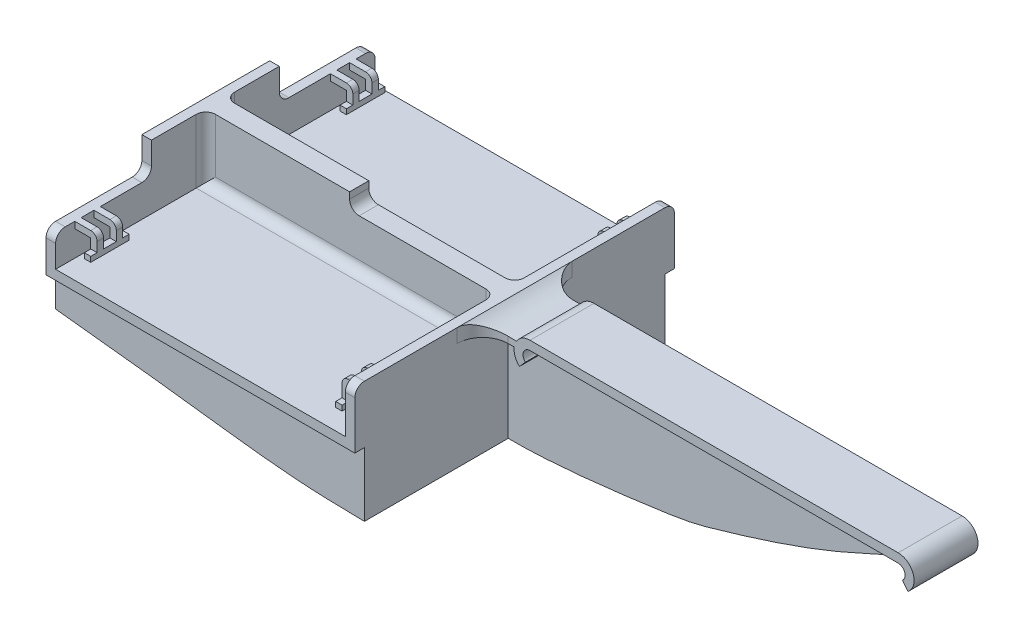
SolidWorks part; units mm, degrees
ref_plane "Piano frontale" through (0, 0, 0) normal (0, 0, 1) x (1, 0, 0)
ref_plane "Piano superiore" through (0, 0, 0) normal (0, 1, 0) x (1, 0, 0)
ref_plane "Piano destro" through (0, 0, 0) normal (1, 0, 0) x (0, 0, -1)
sketch "Schizzo1" plane through (0, 0, 0) normal (0, 0, 1) x (1, 0, 0)
  line L0 (11.7177, -12.3971) -> (506.3844, -12.3971) construction
  line L3 (25.2883, 10.9435) -> (25.2883, 30.9435)
  line L4 (118.9283, 25.9435) -> (118.9283, 7.9435)
  line L5 (118.9283, 7.9435) -> (22.2883, 7.9435)
  line L6 (115.9283, 25.9435) -> (115.9283, 10.9435)
  line L7 (115.9283, 10.9435) -> (25.2883, 10.9435)
  line L8 (22.2883, 7.9435) -> (22.2883, 30.9435)
  line L9 (22.2883, 30.9435) -> (25.2883, 30.9435)
  line L10 (115.9283, 25.9435) -> (118.9283, 25.9435)
  dimension "D1" = 90.64
  dimension "D2" = 20
  dimension "D3" = 15
  dimension "D4" = 3
extrude "Estrusione-Estrusione1" add sketch "Schizzo1" along normal blind 50
sketch "Schizzo2" plane through (25.2883, 0, 0) normal (1, 0, 0) x (0, 0, -1)
  line L0 (-50, 20.9435) -> (-20, 20.9435)
  line L1 (-50, 10.9435) -> (-50, 30.9435) construction
  line L2 (-20, 20.9435) -> (-20, 30.9435)
  line L3 (-50, 30.9435) -> (0, 30.9435) construction
  line L4 (-20, 30.9435) -> (-50, 30.9435)
  line L5 (-50, 30.9435) -> (-50, 20.9435)
  dimension "D1" = 30
  dimension "D2" = 10
extrude "Taglio-Estrusione2" cut sketch "Schizzo2" against normal blind 3
fillet "Raccordo1" radius 3 1 edges at (23.7883, 20.9435, 20)
sketch "Schizzo3" plane through (0, 0, 0) normal (0, 0, -1) x (-1, 0, 0)
  line L0 (-25.2883, 30.9435) -> (-70.2883, 30.9435)
  line L1 (-70.2883, 30.9435) -> (-70.2883, 25.9435)
  line L2 (-70.2883, 25.9435) -> (-115.9283, 25.9435)
  line L3 (-115.9283, 25.9435) -> (-115.9283, 10.9435)
  line L4 (-115.9283, 25.9435) -> (-115.9283, 10.9435) construction
  line L5 (-115.9283, 10.9435) -> (-25.2883, 10.9435) construction
  line L6 (-115.9283, 10.9435) -> (-25.2883, 10.9435)
  line L7 (-25.2883, 10.9435) -> (-25.2883, 30.9435)
  dimension "D1" = 45
  dimension "D2" = 5
extrude "Estrusione-Estrusione2" add sketch "Schizzo3" against normal blind 3
mirror "Specchia1" about plane through (0, 0, 0) normal (0, 0, 1) of "Estrusione-Estrusione2", "Raccordo1", "Taglio-Estrusione2", "Estrusione-Estrusione1"
fillet "Raccordo2" radius 3 7 edges at (70.6083, 10.9435, 3) (70.6083, 10.9435, -3) (115.9283, 18.4435, -3) (115.9283, 18.4435, 3) (70.2883, 25.9435, 0) (25.2883, 20.9435, -3) (25.2883, 20.9435, 3)
sketch "Schizzo4" plane through (25.2883, 0, 0) normal (1, 0, 0) x (0, 0, -1)
  line L0 (-44, 20.9435) -> (-44, 18.9435)
  line L1 (-50, 20.9435) -> (-23, 20.9435) construction
  line L2 (-44, 18.9435) -> (-42, 18.9435)
  line L3 (-42, 18.9435) -> (-42, 20.9435)
  line L4 (-42, 20.9435) -> (-44, 20.9435)
  line L5 (-38, 20.9435) -> (-38, 18.9435)
  line L6 (-38, 18.9435) -> (-36, 18.9435)
  line L7 (-36, 18.9435) -> (-36, 20.9435)
  line L8 (-36, 20.9435) -> (-38, 20.9435)
  dimension "D1" = 2
  dimension "D2" = 2
  dimension "D3" = 2
  dimension "D4" = 2
  dimension "D5" = 6
  dimension "D6" = 4
extrude "Estrusione-Estrusione3" add sketch "Schizzo4" along normal blind 7
sketch "Schizzo6" plane through (0, 18.9435, 0) normal (0, -1, 0) x (1, 0, 0)
  line L0 (32.2883, 44) -> (25.2883, 44) construction
  line L1 (30.2883, 44) -> (32.2883, 44)
  line L2 (30.2883, 44) -> (30.2883, 42)
  line L3 (30.2883, 42) -> (32.2883, 42)
  line L4 (32.2883, 44) -> (32.2883, 42)
  line L5 (32.2883, 38) -> (25.2883, 38) construction
  line L6 (30.2883, 38) -> (32.2883, 38)
  line L7 (30.2883, 38) -> (30.2883, 36)
  line L8 (30.2883, 36) -> (32.2883, 36)
  line L9 (32.2883, 38) -> (32.2883, 36)
  dimension "D1" = 2
  dimension "D2" = 2
extrude "Estrusione-Estrusione5" add sketch "Schizzo6" along normal blind 3
sketch "Schizzo7" plane through (0, 15.9435, 0) normal (0, -1, 0) x (1, 0, 0)
  line L0 (32.2883, 34) -> (32.2883, 46)
  line L1 (32.2883, 46) -> (30.2883, 46)
  line L2 (30.2883, 46) -> (30.2883, 34)
  line L3 (30.2883, 34) -> (32.2883, 34)
  line L4 (32.2883, 36) -> (32.2883, 38) construction
  line L6 (30.2883, 38) -> (30.2883, 36) construction
  dimension "D1" = 2
  dimension "D2" = 2
extrude "Estrusione-Estrusione6" add sketch "Schizzo7" along normal blind 1.62
sketch "Schizzo8" plane through (115.9283, 0, 0) normal (-1, 0, 0) x (0, 0, 1)
  line L0 (50, 10.9435) -> (6, 10.9435) construction
  line L1 (42, 18.9435) -> (44, 18.9435)
  line L2 (42, 18.9435) -> (42, 20.9435)
  line L3 (42, 20.9435) -> (44, 20.9435)
  line L4 (44, 18.9435) -> (44, 20.9435)
  line L5 (36, 20.9435) -> (38, 20.9435)
  line L6 (36, 20.9435) -> (36, 18.9435)
  line L7 (36, 18.9435) -> (38, 18.9435)
  line L8 (38, 20.9435) -> (38, 18.9435)
  line L9 (50, 25.9435) -> (50, 10.9435) construction
  dimension "D1" = 8
  dimension "D2" = 8
  dimension "D3" = 6
  dimension "D4" = 2
  dimension "D5" = 4
  dimension "D6" = 2
  dimension "D7" = 2
  dimension "D8" = 2
extrude "Estrusione-Estrusione7" add sketch "Schizzo8" along normal blind 7
sketch "Schizzo9" plane through (0, 18.9435, 0) normal (0, -1, 0) x (1, 0, 0)
  line L0 (108.9283, 42) -> (115.9283, 42) construction
  line L1 (108.9283, 44) -> (110.9283, 44)
  line L2 (108.9283, 44) -> (108.9283, 42)
  line L3 (108.9283, 42) -> (110.9283, 42)
  line L4 (110.9283, 44) -> (110.9283, 42)
  line L5 (108.9283, 36) -> (115.9283, 36) construction
  line L6 (108.9283, 38) -> (110.9283, 38)
  line L7 (108.9283, 38) -> (108.9283, 36)
  line L8 (108.9283, 36) -> (110.9283, 36)
  line L9 (110.9283, 38) -> (110.9283, 36)
  dimension "D1" = 2
  dimension "D2" = 2
extrude "Estrusione-Estrusione8" add sketch "Schizzo9" along normal blind 4
sketch "Schizzo10" plane through (0, 14.9435, 0) normal (0, -1, 0) x (1, 0, 0)
  line L0 (108.9283, 46) -> (108.9283, 34)
  line L1 (108.9283, 34) -> (110.9283, 34)
  line L2 (110.9283, 34) -> (110.9283, 46)
  line L3 (110.9283, 46) -> (108.9283, 46)
  line L4 (110.9283, 42) -> (110.9283, 44) construction
  dimension "D1" = 2
  dimension "D2" = 2
extrude "Estrusione-Estrusione9" add sketch "Schizzo10" along normal blind 1.62
mirror "Specchia2" about plane through (0, 0, 0) normal (0, 0, 1) of "Estrusione-Estrusione3", "Estrusione-Estrusione5", "Estrusione-Estrusione6", "Estrusione-Estrusione7", "Estrusione-Estrusione8", "Estrusione-Estrusione9"
sketch "Schizzo11" plane through (0, 7.9435, 0) normal (0, -1, 0) x (1, 0, 0)
  line L0 (22.2883, 47) -> (118.9283, 47)
  line L1 (22.2883, 50) -> (22.2883, -50) construction
  line L2 (118.9283, 50) -> (118.9283, -50) construction
  line L4 (118.9283, -47) -> (22.2883, -47)
  line L6 (22.2883, 50) -> (118.9283, 50) construction
  line L7 (22.2883, -50) -> (118.9283, -50) construction
  line L8 (22.2883, 47) -> (22.2883, -47)
  line L9 (118.9283, 47) -> (118.9283, -47)
  dimension "D1" = 3
  dimension "D2" = 3
extrude "Estrusione-Estrusione10" add sketch "Schizzo11" along normal blind 20
sketch "Schizzo12" plane through (0, 0, 47) normal (0, 0, 1) x (1, 0, 0)
  line L0 (13.3941, 1.1199) -> (178.0607, 1.1199) construction
  line L1 (41.1667, 66) -> (205.8333, 66) construction
sketch "Schizzo13" plane through (0, 0, -47) normal (0, 0, -1) x (-1, 0, 0)
  line L0 (25.0297, 53.209) -> (189.6964, 53.209) construction
  line L1 (-22.2883, -12.0565) -> (-22.2883, 7.9435) construction
  line L2 (-118.9283, -12.0565) -> (-22.2883, -12.0565)
  line L3 (-22.2883, -12.0565) -> (-22.2883, -2.8385)
  spline S0 degree 3 poles (-118.9283, -12.0565) (-113.3221, -11.9609) (-97.1539, -11.7038) (-74.9047, -8.9689) (-56.9861, -6.6502) (-40.6543, -4.941) (-29.9124, -3.6877) (-22.2883, -2.8385) knots 0 0 0 0 0.167378 0.482025 0.664557 0.712915 0.965609 0.965609 0.965609 0.965609
extrude "Taglio-Estrusione3" cut sketch "Schizzo13" against normal through all
fillet "Raccordo3" radius 2 8 edges at (32.2883, 20.9435, -37) (32.2883, 20.9435, -43) (108.9283, 20.9435, -37) (108.9283, 20.9435, -43) (108.9283, 20.9435, 37) (108.9283, 20.9435, 43) (32.2883, 20.9435, 43) (32.2883, 20.9435, 37)
sketch "Schizzo15" plane through (118.9283, 0, 0) normal (1, 0, 0) x (0, 0, -1)
  line L0 (0, 25.9435) -> (0, -12.0565) construction
  line L1 (-50, 25.9435) -> (50, 25.9435) construction
  line L2 (47, -12.0565) -> (-47, -12.0565) construction
  line L3 (-2, 25.9435) -> (-2, -13.0023)
  line L5 (2, -13.0023) -> (2, 25.9435)
  line L6 (2, 25.9435) -> (-2, 25.9435)
  line L7 (-2, -13.0023) -> (2, -13.0023)
  dimension "D1" = 2
  dimension "D2" = 2
extrude "Estrusione-Estrusione11" add sketch "Schizzo15" along normal blind 130
sketch "Schizzo16" plane through (0, 0, 2) normal (0, 0, 1) x (1, 0, 0)
  line L0 (248.9283, 25.9435) -> (248.9283, -13.0023) construction
  line L1 (118.9283, -12.0565) -> (118.9283, -13.0023)
  line L2 (118.9283, -13.0023) -> (248.9283, -13.0023)
  line L4 (248.9283, 20.2619) -> (252.8557, 20.2619)
  line L5 (252.8557, 20.2619) -> (252.8557, -13.0023)
  line L6 (252.8557, -13.0023) -> (248.9283, -13.0023)
  spline S0 degree 3 poles (118.9283, -12.0565) (129.6329, -12.2391) (148.9463, -10.2664) (174.9517, -6.6591) (178.1917, -5.9645) (202.7333, 1.4455) (223.4437, 8.7439) (238.8353, 16.6288) (248.9283, 20.2619) knots 0 0 0 0 0.253782 0.311898 0.551242 0.605271 0.822265 1 1 1 1
  spline S1 degree 3 poles (22.2883, -2.8385) (29.9124, -3.6877) (40.6543, -4.941) (56.9861, -6.6502) (74.9047, -8.9689) (97.1539, -11.7038) (113.3221, -11.9609) (118.9283, -12.0565) knots 0 0 0 0 0.252694 0.301053 0.483585 0.798232 0.965609 0.965609 0.965609 0.965609 construction
extrude "Taglio-Estrusione4" cut sketch "Schizzo16" against normal through all
sketch "Schizzo18" plane through (0, 0, 2) normal (0, 0, 1) x (1, 0, 0)
  line L1 (133.7863, 25.9435) -> (118.9283, 25.9435)
  line L2 (248.9283, 25.9435) -> (118.9283, 25.9435) construction
  line L3 (133.7863, 25.9435) -> (133.7863, 23.5598)
  line L4 (133.7863, 23.5598) -> (118.9283, 23.5598)
  line L5 (118.9283, 7.9435) -> (118.9283, 25.9435) construction
  line L6 (118.9283, 23.5598) -> (118.9283, 25.9435)
extrude "Taglio-Estrusione5" cut sketch "Schizzo18" against normal through all
sketch "Schizzo19" plane through (0, 0, 2) normal (0, 0, 1) x (1, 0, 0)
  line L0 (133.7512, 20.9435) -> (248.9283, 20.9435) construction
  line L1 (130.4495, 17.1887) -> (133.7512, 20.9435) construction
  line L2 (133.7512, 25.9435) -> (248.9283, 25.9435)
  line L4 (248.9283, 25.9435) -> (133.7863, 25.9435) construction
  line L7 (248.9283, 25.9435) -> (248.9283, 20.2619) construction
  line L8 (248.9283, 20.9435) -> (252.0069, 17.0036) construction
  arc A0 (133.7512, 25.9435) -> (130.4495, 17.1887) centre (133.7512, 20.9435) ccw
  arc A1 (252.0069, 17.0036) -> (248.9283, 25.9435) centre (248.9283, 20.9435) ccw
  point P4 (191.3398, 20.9435)
extrude "Estrusione-Sottile1" add sketch "Schizzo19" along normal blind 8 and the other way blind 12 thin thin type one direction reverse wall 2.8
sketch "Schizzo21" plane through (0, 0, 2) normal (0, 0, 1) x (1, 0, 0)
  line L2 (253.3512, 19.21) -> (245.348, 19.21)
  arc A0 (253.3512, 19.21) -> (245.348, 19.21) centre (249.3496, 20.8447) ccw
extrude "Estrusione-Estrusione13" add sketch "Schizzo21" against normal blind 4
sketch "Schizzo22" plane through (0, 0, 2) normal (0, 0, 1) x (1, 0, 0)
  line L0 (118.9283, 25.9435) -> (118.9283, 21.6383)
  line L1 (118.9283, 23.5598) -> (118.9283, -12.0565) construction
  line L2 (118.9283, 21.6383) -> (128.9589, 21.6383)
  line L3 (128.9589, 21.6383) -> (129.4903, 23.5598)
  arc A2 (133.7512, 25.9435) -> (130.4495, 17.1887) centre (133.7512, 20.9435) ccw construction
  arc A3 (129.4903, 23.5598) -> (130.4495, 17.1887) centre (133.7512, 20.9435) ccw construction
  spline S1 degree 3 poles (118.9283, 25.9435) (120.3881, 24.8735) (123.9086, 23.5755) (127.6192, 23.5647) (129.4903, 23.5598) knots 0 0 0 0 0.488493 1 1 1 1
  point P2 (128.9589, 21.6383)
extrude "Estrusione-Estrusione14" add sketch "Schizzo22" along normal blind 8 and the other way blind 12
fillet "Raccordo4" radius 8 2 edges at (118.9283, 23.7909, -10) (118.9283, 23.7909, 10)
fillet "Raccordo5" radius 3 4 edges at (23.7883, 20.9435, -50) (117.4283, 25.9435, -50) (117.4283, 25.9435, 50) (23.7883, 20.9435, 50)
